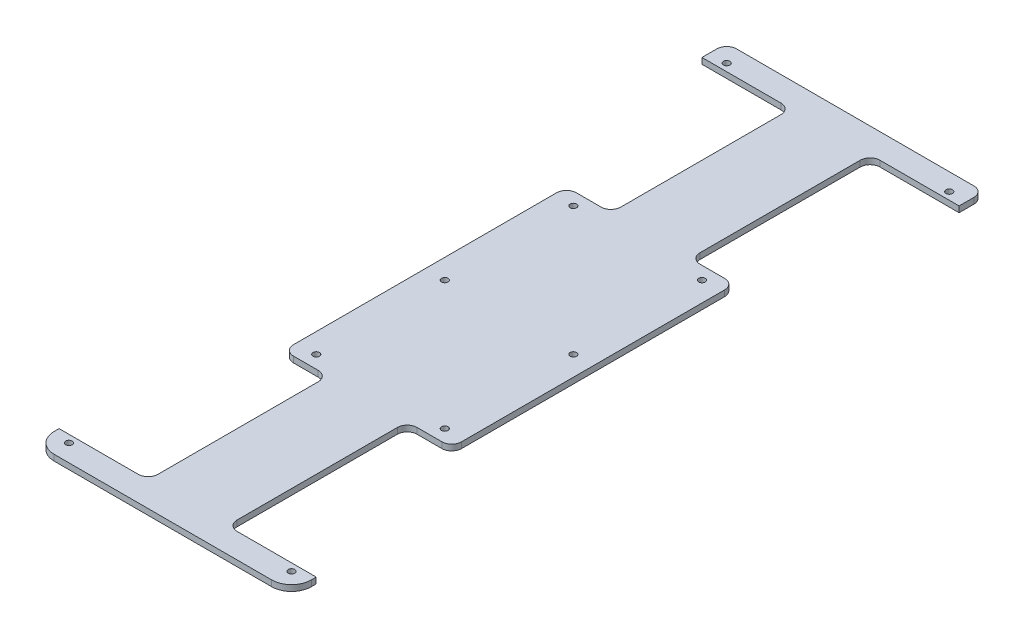
SolidWorks part; units mm, degrees
ref_plane "Front Plane" through (0, 0, 0) normal (0, 0, 1) x (1, 0, 0)
ref_plane "Top Plane" through (0, 0, 0) normal (0, 1, 0) x (1, 0, 0)
ref_plane "Right Plane" through (0, 0, 0) normal (1, 0, 0) x (0, 0, -1)
sketch "Sketch1" plane through (0, 0, 0) normal (0, 1, 0) x (1, 0, 0)
  line L0 (0, 0) -> (130, 0)
  line L1 (0, 0) -> (130, 0) construction
  line L2 (0, 0) -> (0, 350) construction
  line L3 (0, 350) -> (130, 350) construction
  line L4 (130, 0) -> (130, 350) construction
  line L5 (130, 0) -> (130, 12.5)
  line L6 (130, 12.5) -> (85, 12.5)
  line L7 (85, 12.5) -> (85, 103.5)
  line L11 (85, 246.5) -> (85, 337.5)
  line L12 (85, 337.5) -> (130, 337.5)
  line L13 (130, 337.5) -> (130, 350)
  line L14 (130, 350) -> (0, 350)
  line L15 (0, 350) -> (0, 337.5)
  line L16 (0, 337.5) -> (45, 337.5)
  line L17 (45, 337.5) -> (45, 246.5)
  line L21 (45, 103.5) -> (45, 12.5)
  line L22 (45, 12.5) -> (0, 12.5)
  line L23 (0, 12.5) -> (0, 0)
  line L24 (45, 246.5) -> (22.5, 246.5)
  line L25 (22.5, 246.5) -> (22.5, 103.5)
  line L26 (22.5, 103.5) -> (45, 103.5)
  line L27 (85, 246.5) -> (107.5, 246.5)
  line L28 (107.5, 246.5) -> (107.5, 103.5)
  line L29 (107.5, 103.5) -> (85, 103.5)
  dimension "D1" = 130
  dimension "D2" = 350
  dimension "D3" = 45
  dimension "D4" = 91
  dimension "D5" = 22.5
  dimension "D6" = 143
extrude "Boss-Extrude1" add sketch "Sketch1" along normal blind 3
fillet "Fillet1" radius 10 2 edges at (130, 1.5, 0) (0, 1.5, 0)
fillet "Fillet2" radius 5 6 edges at (0, 1.5, -350) (130, 1.5, -350) (107.5, 1.5, -246.5) (107.5, 1.5, -103.5) (22.5, 1.5, -103.5) (22.5, 1.5, -246.5)
sketch "Sketch2" plane through (0, 3, 0) normal (0, 1, 0) x (1, 0, 0)
  line L2 (32.5, 240) -> (32.5, 110) construction
  line L3 (22.5, 175) -> (32.5, 175) construction
  line L4 (22.5, 241.5) -> (22.5, 108.5) construction
  line L5 (65, 350) -> (65, 0) construction
  line L6 (125, 350) -> (5, 350) construction
  line L7 (10, 0) -> (120, 0) construction
  circle A0 centre (32.5, 240) radius 1.65
  circle A1 centre (32.5, 175) radius 1.65
  circle A2 centre (32.5, 110) radius 1.65
  circle A3 centre (97.5, 110) radius 1.65
  circle A4 centre (97.5, 175) radius 1.65
  circle A5 centre (97.5, 240) radius 1.65
  dimension "D3" = 3.3
  dimension "D1" = 10
  dimension "D2" = 130
extrude "Cut-Extrude1" cut sketch "Sketch2" against normal through all
sketch "Sketch3" plane through (0, 3, 0) normal (0, 1, 0) x (1, 0, 0)
  line L0 (0, 12.5) -> (8.75, 12.5) construction
  line L1 (45, 12.5) -> (0, 12.5) construction
  line L2 (8.75, 12.5) -> (8.75, 8.75) construction
  line L3 (65, 0) -> (65, 57.6288) construction
  line L4 (10, 0) -> (120, 0) construction
  circle A0 centre (8.75, 8.75) radius 1.65
  circle A1 centre (121.25, 8.75) radius 1.65
  dimension "D3" = 3.3
  dimension "D1" = 8.75
  dimension "D2" = 3.75
extrude "Cut-Extrude2" cut sketch "Sketch3" against normal through all
sketch "Sketch4" plane through (0, 3, 0) normal (0, 1, 0) x (1, 0, 0)
  line L0 (0, 337.5) -> (8.75, 337.5) construction
  line L1 (0, 337.5) -> (45, 337.5) construction
  line L2 (8.75, 337.5) -> (8.75, 341.25) construction
  line L3 (65, 350) -> (65, 288.2737) construction
  line L4 (125, 350) -> (5, 350) construction
  circle A0 centre (8.75, 341.25) radius 1.65
  circle A1 centre (121.25, 341.25) radius 1.65
  dimension "D3" = 3.3
  dimension "D1" = 8.75
  dimension "D2" = 3.75
extrude "Cut-Extrude3" cut sketch "Sketch4" against normal through all
fillet "Fillet3" radius 5 8 edges at (85, 1.5, -246.5) (45, 1.5, -246.5) (85, 1.5, -103.5) (45, 1.5, -103.5) (45, 1.5, -12.5) (85, 1.5, -12.5) (45, 1.5, -337.5) (85, 1.5, -337.5)
